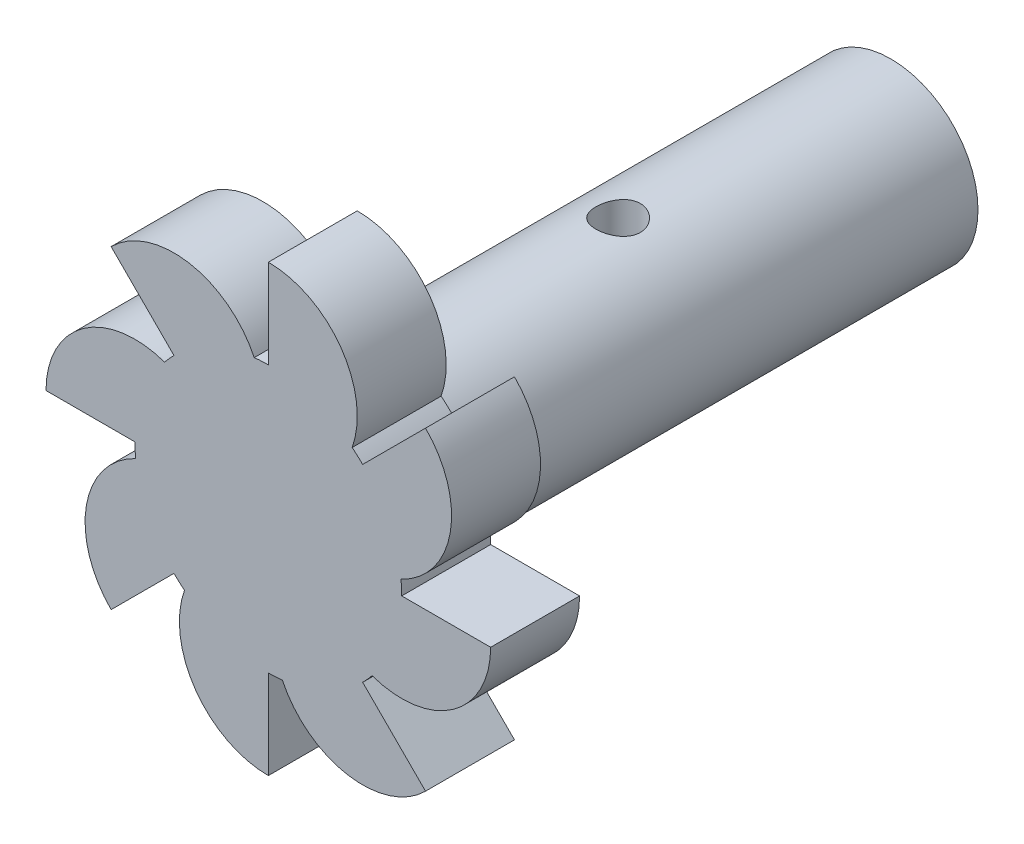
SolidWorks part; units mm, degrees
ref_plane "Front Plane" through (0, 0, 0) normal (0, 0, 1) x (1, 0, 0)
ref_plane "Top Plane" through (0, 0, 0) normal (0, 1, 0) x (1, 0, 0)
ref_plane "Right Plane" through (0, 0, 0) normal (1, 0, 0) x (0, 0, -1)
sketch "Sketch1" plane through (0, 0, 0) normal (0, 0, 1) x (1, 0, 0)
  circle A0 centre (0, 0) radius 9.8
  dimension "D1" = 19.6
extrude "Boss-Extrude1" add sketch "Sketch1" along normal blind 60
sketch "Sketch2" plane through (0, 0, 60) normal (0, 0, 1) x (1, 0, 0)
  line L0 (0, 25) -> (0, 15)
  line L1 (17.6777, 17.6777) -> (10.6066, 10.6066)
  line L2 (25, 0) -> (15, 0)
  line L3 (17.6777, -17.6777) -> (10.6066, -10.6066)
  line L4 (0, -25) -> (0, -15)
  line L5 (-17.6777, -17.6777) -> (-10.6066, -10.6066)
  line L6 (-25, 0) -> (-15, 0)
  line L7 (-17.6777, 17.6777) -> (-10.6066, 10.6066)
  arc A1 (0, 25) -> (9.4281, 11.6667) centre (0, 15) cw
  arc A2 (0, 15) -> (-1.5829, 14.9162) centre (0, 0) ccw
  arc A3 (17.6777, 17.6777) -> (14.9162, 1.5829) centre (10.6066, 10.6066) cw
  arc A4 (25, 0) -> (11.6667, -9.4281) centre (15, 0) cw
  arc A5 (17.6777, -17.6777) -> (1.5829, -14.9162) centre (10.6066, -10.6066) cw
  arc A6 (0, -25) -> (-9.4281, -11.6667) centre (0, -15) cw
  arc A7 (-17.6777, -17.6777) -> (-14.9162, -1.5829) centre (-10.6066, -10.6066) cw
  arc A8 (-25, 0) -> (-11.6667, 9.4281) centre (-15, 0) cw
  arc A9 (-17.6777, 17.6777) -> (-1.5829, 14.9162) centre (-10.6066, 10.6066) cw
  arc A10 (10.6066, 10.6066) -> (9.4281, 11.6667) centre (0, 0) ccw
  arc A11 (15, 0) -> (14.9162, 1.5829) centre (0, 0) ccw
  arc A12 (10.6066, -10.6066) -> (11.6667, -9.4281) centre (0, 0) ccw
  arc A13 (0, -15) -> (1.5829, -14.9162) centre (0, 0) ccw
  arc A14 (-10.6066, -10.6066) -> (-9.4281, -11.6667) centre (0, 0) ccw
  arc A15 (-15, 0) -> (-14.9162, -1.5829) centre (0, 0) ccw
  arc A16 (-10.6066, 10.6066) -> (-11.6667, 9.4281) centre (0, 0) ccw
  point P31 (0, 0)
  dimension "D2" = 10
  dimension "D3" = 8
extrude "Boss-Extrude3" add sketch "Sketch2" along normal blind 10
fillet "Fillet2" radius 1 1 edges at (9.8, 0, 60)
sketch "Sketch3" plane through (0, 0, 0) normal (0, 0, -1) x (-1, 0, 0)
  circle A0 centre (0, 0) radius 6
  dimension "D1" = 12
extrude "Cut-Extrude1" cut sketch "Sketch3" against normal blind 20
thread "Thread1" start angle 0, offset 0, length 0, pitch 1.75, diameter 12
ref_plane "Plane1" through (6, 0, 0) normal (0, -1, 0) x (1, 0, 0)
sketch "Thread Profile1" plane through (6, 0, 0) normal (0, -1, 0) x (1, 0, 0)
  line L0 (0, 0) -> (0, 1.75) construction
  line L11 (0, 0) -> (0, 1.5312)
  line L12 (0, 1.5312) -> (-0.9472, 0.9844)
  line L13 (-0.9472, 0.9844) -> (-0.9472, 0.5469)
  line L15 (-0.9472, 0.5469) -> (0, 0)
  line L17 (-0.9472, 0.7656) -> (0, 0.7656) construction
  point P2 (0, 0)
  dimension "Pitch" = 1.75
  dimension "Profile_Angle" = 60
  dimension "Profile_Land" = 0.4375
  dimension "Profile_Height" = 0.9472
sketch "Sketch4" plane through (0, 0, 0) normal (0, 1, 0) x (1, 0, 0)
  circle A0 centre (0, -30.6679) radius 2.5
  point P2 (0, -30.6679)
  dimension "D1" = 5
extrude "Cut-Extrude2" cut sketch "Sketch4" against normal mid plane 30
